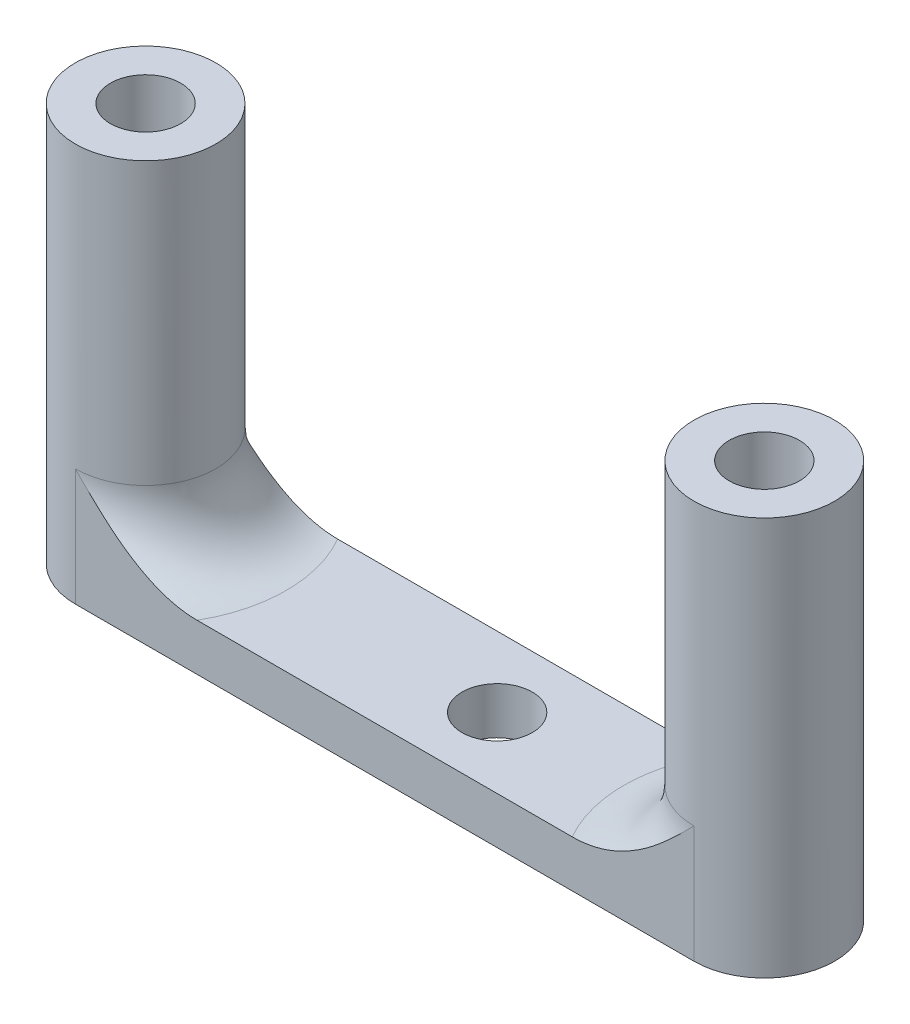
SolidWorks part; units mm, degrees
ref_plane "Front Plane" through (0, 0, 0) normal (0, 0, 1) x (1, 0, 0)
ref_plane "Top Plane" through (0, 0, 0) normal (0, 1, 0) x (1, 0, 0)
ref_plane "Right Plane" through (0, 0, 0) normal (1, 0, 0) x (0, 0, -1)
sketch "Sketch1" plane through (0, 0, 0) normal (0, 1, 0) x (1, 0, 0)
  line L0 (0, 0) -> (26.4, 0)
  line L1 (0, 3) -> (26.4, 3)
  line L2 (0, -3) -> (26.4, -3)
  arc A0 (0, 3) -> (0, -3) centre (0, 0) ccw
  arc A1 (26.4, -3) -> (26.4, 3) centre (26.4, 0) ccw
  circle A2 centre (0, 0) radius 1.5
  circle A3 centre (26.4, 0) radius 1.5
  circle A4 centre (15, 0) radius 1.5
  dimension "D1" = 6
  dimension "D3" = 3
  dimension "D2" = 26.4
  dimension "D4" = 15
extrude "Boss-Extrude1" add sketch "Sketch1" along normal blind 2 contours L2 A1 L1 A0 A4 A3 A2 region at (13.2, 0, -2.6705)
sketch "Sketch2" plane through (0, 2, 0) normal (0, 1, 0) x (1, 0, 0)
  circle A0 centre (0, 0) radius 1.5 construction
  circle A1 centre (0, 0) radius 1.5
  circle A2 centre (26.4, 0) radius 1.5 construction
  circle A3 centre (26.4, 0) radius 1.5
  circle A4 centre (0, 0) radius 3
  circle A5 centre (26.4, 0) radius 3
  dimension "D1" = 1.5
extrude "Boss-Extrude2" add sketch "Sketch2" along normal blind 15
fillet "Fillet1" radius 3 2 edges at (23.4, 2, 0) (3, 2, 0)
